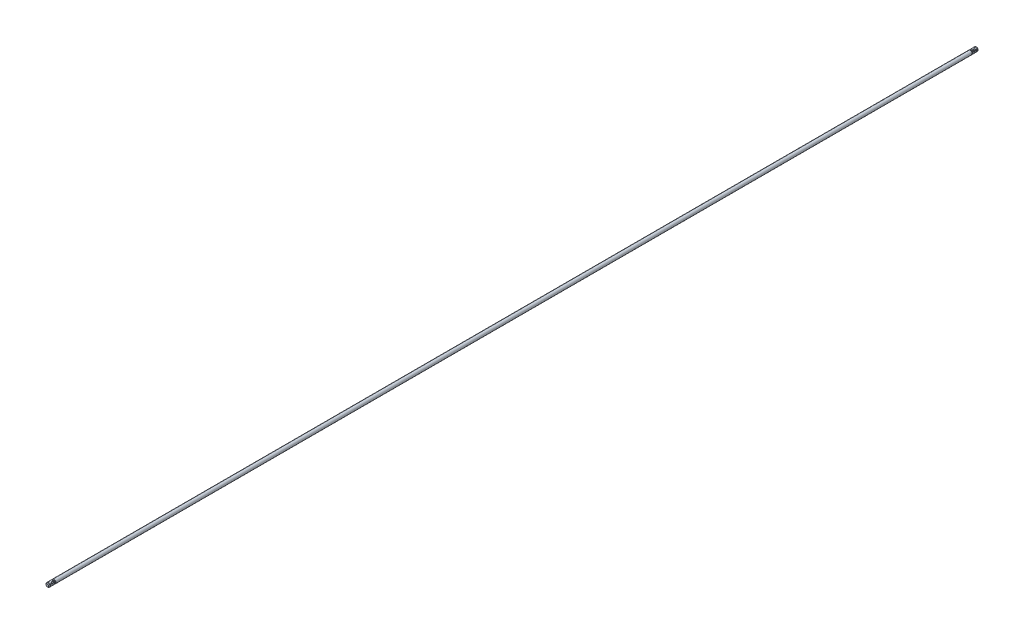
SolidWorks part; units mm, degrees
ref_plane "Спереди" through (0, 0, 0) normal (0, 0, 1) x (1, 0, 0)
ref_plane "Сверху" through (0, 0, 0) normal (0, 1, 0) x (1, 0, 0)
ref_plane "Справа" through (0, 0, 0) normal (1, 0, 0) x (0, 0, -1)
sketch "Эскиз2" plane through (0, 0, 0) normal (0, 0, 1) x (1, 0, 0)
  circle A0 centre (0, 0) radius 3
  dimension "D1" = 6
extrude "Бобышка-Вытянуть1" add sketch "Эскиз2" against normal blind 711 and the other way blind 711 contours A0
chamfer "Фаска1" distance 1 angle 45 1 edges at (3, 0, 711)
thread "Резьба1" pitch 1 method cut profile "Профиль резьбы2" start angle 0, offset 0, length 9, pitch 1, diameter 6
ref_plane "Плоскость5" through (-3, 0, 710) normal (0, -1, 0) x (-1, 0, 0)
sketch "Профиль резьбы2" plane through (-3, 0, 710) normal (0, -1, 0) x (-1, 0, 0)
  line L0 (0, 0) -> (0, 1) construction
  line L11 (0, 0) -> (0, 0.875)
  line L12 (0, 0.875) -> (-0.5413, 0.5625)
  line L13 (-0.5413, 0.5625) -> (-0.5413, 0.3125)
  line L15 (-0.5413, 0.3125) -> (0, 0)
  line L17 (-0.5413, 0.4375) -> (0, 0.4375) construction
  point P2 (0, 0)
  dimension "Pitch" = 1
  dimension "Profile_Angle" = 60
  dimension "Profile_Land" = 0.25
  dimension "Profile_Height" = 0.5413
chamfer "Фаска2" distance 1 angle 45 1 edges at (3, 0, -711)
thread "Резьба2" pitch 1 method cut profile "Профиль резьбы3" start angle 0, offset 0, length 9, pitch 1, diameter 6
ref_plane "Плоскость6" through (3, 0, -710) normal (0, -1, 0) x (1, 0, 0)
sketch "Профиль резьбы3" plane through (3, 0, -710) normal (0, -1, 0) x (1, 0, 0)
  line L0 (0, 0) -> (0, 1) construction
  line L11 (0, 0) -> (0, 0.875)
  line L12 (0, 0.875) -> (-0.5413, 0.5625)
  line L13 (-0.5413, 0.5625) -> (-0.5413, 0.3125)
  line L15 (-0.5413, 0.3125) -> (0, 0)
  line L17 (-0.5413, 0.4375) -> (0, 0.4375) construction
  point P2 (0, 0)
  dimension "Pitch" = 1
  dimension "Profile_Angle" = 60
  dimension "Profile_Land" = 0.25
  dimension "Profile_Height" = 0.5413
